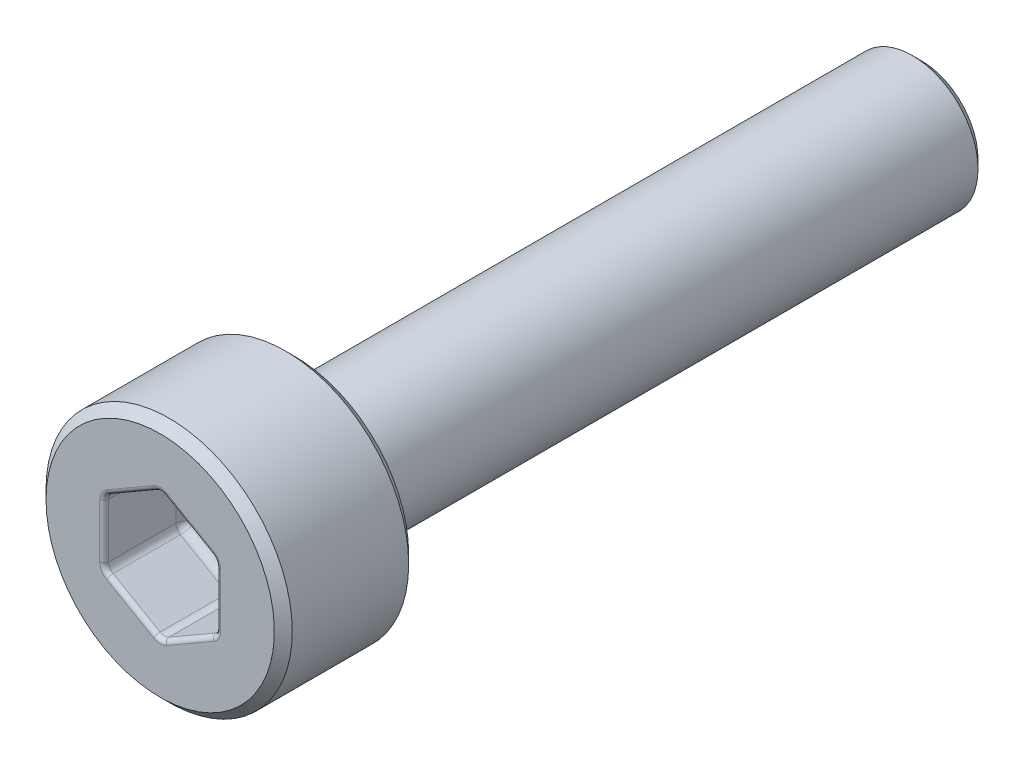
SolidWorks part; units mm, degrees
material "1.4000 (X6Cr13)"
ref_plane "Ebene vorne" through (0, 0, 0) normal (0, 0, 1) x (1, 0, 0)
ref_plane "Ebene oben" through (0, 0, 0) normal (0, 1, 0) x (1, 0, 0)
ref_plane "Ebene rechts" through (0, 0, 0) normal (1, 0, 0) x (0, 0, -1)
sketch "Skizze1" plane through (0, 0, 0) normal (1, 0, 0) x (0, 0, -1)
  line L0 (-21.9199, 0) -> (33.7608, 0) construction
  line L1 (0, 13.9907) -> (0, -9.4798) construction
  line L2 (-3, 0) -> (-3, 2.75)
  line L3 (-3, 2.75) -> (0, 2.75)
  line L4 (0, 2.75) -> (0, 1.465)
  line L5 (0, 1.465) -> (14, 1.465)
  line L6 (14, 1.465) -> (14, 0)
  line L7 (14, 0) -> (-3, 0)
  dimension "D1" = 2.93
  dimension "D2" = 3
  dimension "D3" = 5.5
  dimension "D4" = 14
revolve "Rotation1" add sketch "Skizze1" angle 360 about L0
sketch "Skizze2" plane through (0, 0, 3) normal (0, 0, 1) x (1, 0, 0)
  line L0 (0, 8.6995) -> (0, -7.3778) construction
  line L1 (1.25, -0.7217) -> (1.25, 0.7217)
  line L2 (1.25, 0.7217) -> (0, 1.4434)
  line L3 (0, 1.4434) -> (-1.25, 0.7217)
  line L4 (-1.25, 0.7217) -> (-1.25, -0.7217)
  line L5 (-1.25, -0.7217) -> (0, -1.4434)
  line L6 (0, -1.4434) -> (1.25, -0.7217)
  circle A0 centre (0, 0) radius 1.25 construction
  dimension "D1" = 2.5
extrude "Schnitt-Linear austragen1" cut sketch "Skizze2" against normal blind 1.8
chamfer "Fase1" distance 0.2 angle 45 3 edges at (2.75, 0, 3) (2.75, 0, 0) (1.465, 0, -14)
fillet "Verrundung1" radius 0.2 13 edges at (-0.625, -1.0825, 1.2) (-1.25, 0, 1.2) (-0.625, 1.0825, 1.2) (0.625, 1.0825, 1.2) (1.25, 0, 1.2) (0.625, -1.0825, 1.2) (-1.25, -0.7217, 2.1) (0, -1.4434, 2.1) (1.25, -0.7217, 2.1) (1.25, 0.7217, 2.1) (0, 1.4434, 2.1) (-1.25, 0.7217, 2.1) (1.465, 0, 0)
fillet "Verrundung2" radius 0.1 12 edges at (1.2232, -0.7062, 3) (0.625, -1.0825, 3) (0, -1.4124, 3) (-0.625, -1.0825, 3) (-1.2232, -0.7062, 3) (-1.25, 0, 3) (-1.2232, 0.7062, 3) (-0.625, 1.0825, 3) (0, 1.4124, 3) (0.625, 1.0825, 3) (1.2232, 0.7062, 3) (1.25, 0, 3)
ref_axis "Achse1" through (0, 0, -19.6323) along (0, 0, 1)
